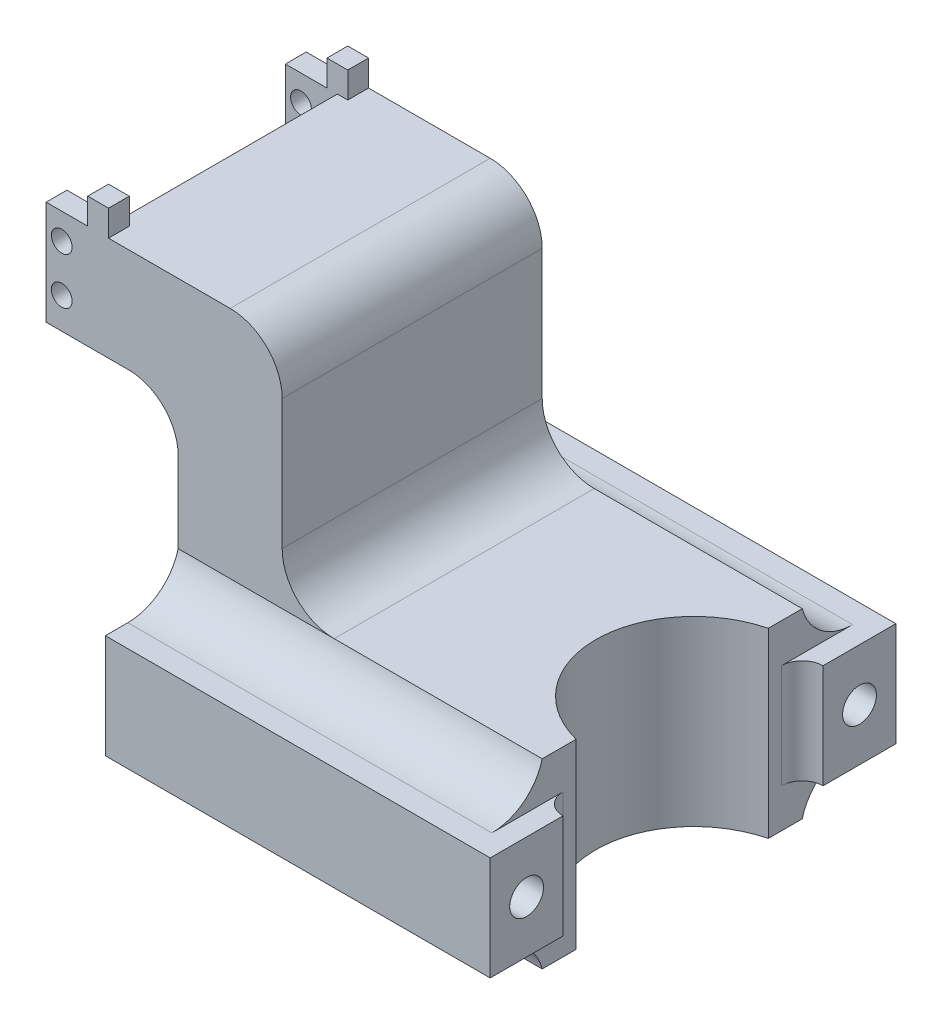
SolidWorks part; units mm, degrees
ref_plane "Front Plane" through (0, 0, 0) normal (0, 0, 1) x (1, 0, 0)
ref_plane "Top Plane" through (0, 0, 0) normal (0, 1, 0) x (1, 0, 0)
ref_plane "Right Plane" through (0, 0, 0) normal (1, 0, 0) x (0, 0, -1)
sketch "Sketch1" plane through (0, 0, 0) normal (0, 1, 0) x (1, 0, 0)
  line L1 (-25, 25) -> (25, 25)
  line L2 (-25, 25) -> (-25, -25)
  line L3 (-25, -25) -> (25, -25)
  line L4 (25, 25) -> (25, -25)
  line L5 (-25, 25) -> (25, -25) construction
  line L6 (-25, -25) -> (25, 25) construction
  ellipse E0 centre (0, 0) end of major axis (19.7, 0) minor radius 19.1
  dimension "D1" = 39.4
  dimension "D2" = 38.2
  dimension "D3" = 50
  dimension "D4" = 50
extrude "Boss-Extrude1" add sketch "Sketch1" along normal blind 35
sketch "Sketch2" plane through (0, 35, 0) normal (0, 1, 0) x (1, 0, 0)
  line L0 (25, 25) -> (-25, 25) construction
  line L1 (-5, 25) -> (25, 25)
  line L2 (-5, 25) -> (-5, -25)
  line L3 (-5, -25) -> (25, -25)
  line L4 (25, 25) -> (25, -25)
  dimension "D1" = 30
extrude "Cut-Extrude1" cut sketch "Sketch2" against normal blind 35
sketch "Sketch3" plane through (0, 35, 0) normal (0, 1, 0) x (1, 0, 0)
  line L0 (-25, -25) -> (-5, -25) construction
  line L1 (-25, 25) -> (-12, 25)
  line L2 (-25, 25) -> (-25, -25)
  line L3 (-25, -25) -> (-12, -25)
  line L4 (-12, 25) -> (-12, -25)
  dimension "D1" = 13
extrude "Boss-Extrude2" add sketch "Sketch3" along normal blind 20
sketch "Sketch4" plane through (-25, 0, 0) normal (-1, 0, 0) x (0, 0, 1)
  line L4 (18.4746, 0) -> (18.4746, 35)
  line L5 (-18.4746, 0) -> (18.4746, 0)
  line L6 (-18.4746, 35) -> (-18.4746, 0)
  line L7 (-15.1475, 35) -> (-18.4746, 35)
  line L8 (18.4746, 0) -> (18.4746, 35)
  line L9 (-18.4746, 0) -> (18.4746, 0)
  line L10 (-18.4746, 35) -> (-18.4746, 0)
  line L11 (-15.1475, 35) -> (-18.4746, 35)
  line L14 (15.1475, 35) -> (-15.1475, 35)
  line L16 (15.1475, 35) -> (-15.1475, 35)
  line L18 (18.4746, 35) -> (15.1475, 35)
  line L20 (18.4746, 35) -> (15.1475, 35)
  circle A0 centre (18.4746, 50) radius 1.5
  dimension "D3" = 3
  dimension "D1" = 0
extrude "Cut-Extrude2" cut sketch "Sketch4" against normal through all contours A0 region at (-25, 50, 18.4746)
ref_plane "Plane1" through (-12, 55, -25) normal (-1, 0, 0) x (0, 0, 1)
sketch "Sketch5" plane through (-12, 55, -25) normal (-1, 0, 0) x (0, 0, 1)
  line L1 (0, 0) -> (36.9746, 0)
  line L2 (0, 0) -> (0, -20)
  line L3 (0, -20) -> (36.9746, -20)
  line L4 (0, -55) -> (50, -55)
  line L5 (50, -55) -> (50, 0)
  line L6 (50, 0) -> (0, 0)
  line L7 (0, 0) -> (0, -55)
  line L8 (0, -55) -> (50, -55)
  line L9 (50, -55) -> (50, 0)
  line L11 (0, 0) -> (0, -55) construction
  line L12 (43.4746, -55) -> (43.4746, -20)
  line L13 (6.5254, -55) -> (43.4746, -55)
  line L14 (6.5254, -20) -> (6.5254, -55)
  line L15 (9.8525, -20) -> (6.5254, -20)
  line L16 (43.4746, -55) -> (43.4746, -20) construction
  line L17 (6.5254, -55) -> (43.4746, -55)
  line L18 (6.5254, -20) -> (6.5254, -55) construction
  line L19 (9.8525, -20) -> (6.5254, -20) construction
  line L20 (36.9746, 0) -> (36.9746, -20)
  line L24 (50, 0) -> (0, 0)
  line L27 (40.1475, -20) -> (9.8525, -20)
  line L28 (40.1475, -20) -> (9.8525, -20)
  line L29 (43.4746, -20) -> (40.1475, -20)
  line L30 (43.4746, -20) -> (40.1475, -20)
  circle A0 centre (43.4746, -5) radius 1.5 construction
  dimension "D3" = 6.5
  dimension "D1" = 0
  dimension "D2" = 0
extrude "Cut-Extrude3" cut sketch "Sketch5" along normal blind 20 contours L20 L1 L2 L3 region at (-12, 45, -6.5127)
sketch "Sketch6" plane through (-5, 0, 0) normal (1, 0, 0) x (0, 0, -1)
  line L0 (-25, 35) -> (-25, 0) construction
  line L1 (25, 0) -> (25, 35) construction
  line L2 (-39, 27.5) -> (-25, 27.5)
  line L3 (-39, 27.5) -> (-39, 7.5)
  line L4 (-39, 7.5) -> (-25, 7.5)
  line L5 (-25, 27.5) -> (-25, 7.5)
  line L6 (-39, 27.5) -> (-25, 7.5) construction
  line L7 (-39, 7.5) -> (-25, 27.5) construction
  line L8 (39, 7.5) -> (25, 7.5)
  line L9 (39, 7.5) -> (39, 27.5)
  line L10 (39, 27.5) -> (25, 27.5)
  line L11 (25, 7.5) -> (25, 27.5)
  line L12 (39, 7.5) -> (25, 27.5) construction
  line L13 (39, 27.5) -> (25, 7.5) construction
  line L14 (32, 17.5) -> (-26.1195, 17.5) construction
  circle A0 centre (32, 17.5) radius 3.25
  circle A1 centre (-32, 17.5) radius 3.25
  point P4 (-32, 17.5)
  point P9 (32, 17.5)
  point P17 (-25, 17.5)
  point P18 (-25, 17.5)
  point P19 (25, 17.5)
  point P20 (25, 17.5)
  dimension "D4" = 6.5
  dimension "D5" = 6.5
  dimension "D2" = 20
  dimension "D1" = 14
  dimension "D3" = 14
extrude "Boss-Extrude3" add sketch "Sketch6" along normal blind 4 and the other way blind 20
sketch "Sketch7" plane through (-25, 0, 0) normal (-1, 0, 0) x (0, 0, 1)
  circle A0 centre (-32, 17.5) radius 5.3
  circle A1 centre (32, 17.5) radius 5.3
  circle A2 centre (18.4746, 50) radius 3
  dimension "D1" = 10.6
  dimension "D2" = 10.6
  dimension "D3" = 6
extrude "Cut-Extrude4" cut sketch "Sketch7" against normal blind 6
sketch "Sketch8" plane through (0, 35, 0) normal (0, 1, 0) x (1, 0, 0)
  line L4 (-12, -11.9746) -> (-25, -11.9746)
  line L5 (-25, -11.9746) -> (-25, -25)
  line L6 (-25, -25) -> (-12, -25)
  line L7 (-12, -25) -> (-12, -11.9746)
  line L8 (-12, -11.9746) -> (-25, -11.9746)
  line L9 (-25, -11.9746) -> (-25, -25)
  line L10 (-25, -25) -> (-12, -25)
  line L11 (-12, -25) -> (-12, -11.9746)
  dimension "D1" = 0
extrude "Cut-Extrude5" cut sketch "Sketch8" along normal blind 30
fillet "Fillet6" radius 4 2 edges at (-5, 17.5, 25) (-5, 17.5, -25)
fillet "Fillet5" radius 10 4 edges at (-15, 7.5, 25) (-15, 27.5, 25) (-15, 27.5, -25) (-15, 7.5, -25)
sketch "Sketch9" plane through (-25, 0, 0) normal (-1, 0, 0) x (0, 0, 1)
  line L8 (39, 27.5) -> (34.6825, 27.5)
  line L9 (25, 35) -> (-25, 35)
  line L10 (-34.6825, 27.5) -> (-39, 27.5)
  line L11 (-39, 27.5) -> (-39, 7.5)
  line L12 (-39, 7.5) -> (-34.6825, 7.5)
  line L13 (-25, 0) -> (25, 0)
  line L14 (34.6825, 7.5) -> (39, 7.5)
  line L15 (39, 7.5) -> (39, 27.5)
  line L16 (39, 27.5) -> (34.6825, 27.5)
  line L17 (25, 35) -> (-25, 35)
  line L18 (-34.6825, 27.5) -> (-39, 27.5)
  line L19 (-39, 27.5) -> (-39, 7.5)
  line L20 (-39, 7.5) -> (-34.6825, 7.5)
  line L21 (-25, 0) -> (25, 0)
  line L22 (34.6825, 7.5) -> (39, 7.5)
  line L23 (39, 7.5) -> (39, 27.5)
  circle A0 centre (32, 17.5) radius 5.3 construction
  circle A1 centre (-32, 17.5) radius 5.3 construction
  circle A2 centre (32, 17.5) radius 5.3
  circle A3 centre (-32, 17.5) radius 5.3
  arc A4 (25, 35) -> (34.6825, 27.5) centre (34.6825, 37.5) ccw
  arc A5 (-34.6825, 27.5) -> (-25, 35) centre (-34.6825, 37.5) ccw
  arc A6 (-25, 0) -> (-34.6825, 7.5) centre (-34.6825, -2.5) ccw
  arc A7 (34.6825, 7.5) -> (25, 0) centre (34.6825, -2.5) ccw
  arc A8 (25, 35) -> (34.6825, 27.5) centre (34.6825, 37.5) ccw
  arc A9 (-34.6825, 27.5) -> (-25, 35) centre (-34.6825, 37.5) ccw
  arc A10 (-25, 0) -> (-34.6825, 7.5) centre (-34.6825, -2.5) ccw
  arc A11 (34.6825, 7.5) -> (25, 0) centre (34.6825, -2.5) ccw
  dimension "D1" = 0
extrude "Boss-Extrude4" add sketch "Sketch9" along normal blind 50
sketch "Sketch10" plane through (0, 35, 0) normal (0, 1, 0) x (1, 0, 0)
  line L5 (-75, -25) -> (-5, -25) construction
  line L6 (-75, 25) -> (-55, 25)
  line L7 (-75, 25) -> (-75, -25)
  line L8 (-75, -25) -> (-55, -25)
  line L9 (-55, 25) -> (-55, -25)
  dimension "D1" = 20
extrude "Boss-Extrude5" add sketch "Sketch10" along normal blind 45
fillet "Fillet7" radius 10 1 edges at (-55, 35, 0)
sketch "Sketch11" plane through (-75, 0, 0) normal (-1, 0, 0) x (0, 0, 1)
  line L5 (25, 80) -> (25, 35) construction
  line L6 (-25, 80) -> (25, 80)
  line L7 (-25, 80) -> (-25, 60)
  line L8 (-25, 60) -> (25, 60)
  line L9 (25, 80) -> (25, 60)
  dimension "D1" = 20
extrude "Boss-Extrude6" add sketch "Sketch11" along normal blind 85
fillet "Fillet8" radius 9.5 1 edges at (-75, 60, 0)
sketch "Sketch13" plane through (0, 80, 0) normal (0, 1, 0) x (1, 0, 0)
  line L0 (-85, 25) -> (-85, -25) construction
  line L1 (-55, 25) -> (-160, 25) construction
  line L2 (-55, 25) -> (-160, 25) construction
  line L3 (-160, -25) -> (-55, -25) construction
  line L4 (-85, 0) -> (-160, 0) construction
  line L5 (-160, 25) -> (-150.4508, 25)
  line L6 (-160, 25) -> (-160, -25)
  line L7 (-160, -25) -> (-150.4508, -25)
  line L8 (-160, -25) -> (-160, 25) construction
  circle A0 centre (-122.5, 0) radius 37.5
  point P4 (-150.4508, 25)
  point P19 (-160, 0)
  line M2 (-55, 25) -> (-160, 25)
  line M14 (-160, -25) -> (-55, -25)
  line M16 (-160, 25) -> (-160, -25)
  dimension "D2" = 75
  dimension "D1" = 75
extrude "Boss-Extrude7" add sketch "Sketch13" against normal up to surface (20 mm away) contours A0 M2 | A0 | A0 region at (-122.5, 80, -30.0791) up to face at (-122.25, 60, 0)
extrude "Cut-Extrude6" cut sketch "Sketch13<3>" against normal blind 85 contours A0 L6 M14 | A0 M2 M16 region at (-157.2108, 80, -18.9204) region at (-157.2108, 80, 18.9204)
sketch "Sketch13<3>" plane through (0, 80, 0) normal (0, 1, 0) x (1, 0, 0) same geometry as "Sketch13"
fillet "Fillet9" radius 10 2 edges at (-94.5492, 70, -25) (-94.5492, 70, 25)
fillet "Fillet10" radius 10 1 edges at (-55, 80, 0)
sketch "Sketch14" plane through (0, 80, 0) normal (0, 1, 0) x (1, 0, 0)
  line L0 (-122.5, 25) -> (-122.5, -25) construction
  line L1 (-122.5, -25) -> (-97.5, 0) construction
  line L2 (-97.5, 0) -> (-122.5, 25) construction
  line L3 (-122.5, 25) -> (-147.5, 0) construction
  line L4 (-147.5, 0) -> (-97.5, 0) construction
  line L5 (-147.5, 0) -> (-122.5, -25) construction
  line L6 (-140.1777, -17.6777) -> (-104.8223, 17.6777) construction
  line L7 (-140.1777, 17.6777) -> (-104.8223, -17.6777) construction
  circle A0 centre (-122.5, 0) radius 25 construction
  circle A1 centre (-140.1777, 17.6777) radius 3.25
  circle A2 centre (-140.1777, -17.6777) radius 3.25
  circle A3 centre (-104.8223, -17.6777) radius 3.25
  circle A4 centre (-104.8223, 17.6777) radius 3.25
  point P10 (-122.5, 0)
  point P13 (-122.5, 0)
  dimension "D4" = 6.5
  dimension "D5" = 6.5
  dimension "D1" = 50
  dimension "D2" = 6.5
  dimension "D3" = 6.5
extrude "Cut-Extrude7" cut sketch "Sketch14" against normal blind 85
sketch "Sketch15" plane through (0, 80, 0) normal (0, 1, 0) x (1, 0, 0)
  circle A0 centre (-140.1777, 17.6777) radius 5.3
  circle A1 centre (-140.1777, -17.6777) radius 5.3
  circle A2 centre (-104.8223, -17.6777) radius 5.3
  circle A3 centre (-104.8223, 17.6777) radius 5.3
  dimension "D1" = 10.6
  dimension "D2" = 10.6
  dimension "D3" = 10.6
  dimension "D4" = 10.6
extrude "Cut-Extrude8" cut sketch "Sketch15" against normal blind 7
sketch "Sketch16" plane through (-75, 0, 0) normal (-1, 0, 0) x (0, 0, 1)
  line L1 (-25.9378, 17.5) -> (-28.9689, 22.75)
  line L2 (-28.9689, 22.75) -> (-35.0311, 22.75)
  line L3 (-35.0311, 22.75) -> (-38.0622, 17.5)
  line L4 (-38.0622, 17.5) -> (-35.0311, 12.25)
  line L5 (-35.0311, 12.25) -> (-28.9689, 12.25)
  line L6 (-28.9689, 12.25) -> (-25.9378, 17.5)
  line L7 (25.9378, 17.5) -> (28.9689, 12.25)
  line L8 (28.9689, 12.25) -> (35.0311, 12.25)
  line L9 (35.0311, 12.25) -> (38.0622, 17.5)
  line L10 (38.0622, 17.5) -> (35.0311, 22.75)
  line L11 (35.0311, 22.75) -> (28.9689, 22.75)
  line L12 (28.9689, 22.75) -> (25.9378, 17.5)
  circle A0 centre (-32, 17.5) radius 5.25 construction
  circle A1 centre (32, 17.5) radius 5.25 construction
  circle A2 centre (32, 17.5) radius 3.25 construction
  circle A3 centre (-32, 17.5) radius 3.25 construction
  circle A4 centre (32, 17.5) radius 3.25
  circle A5 centre (-32, 17.5) radius 3.25
  dimension "D1" = 10.5
  dimension "D2" = 10.5
extrude "Boss-Extrude9" add sketch "Sketch16" against normal up to surface (56 mm away) up to face at (-19, 17.5, -26.7)
extrude "Cut-Extrude11" cut sketch "Sketch16<3>" against normal blind 10
sketch "Sketch16<3>" plane through (-75, 0, 0) normal (-1, 0, 0) x (0, 0, 1) same geometry as "Sketch16"
ref_plane "Plane2" through (-160, 0, 0) normal (-1, 0, 0) x (0, 0, 1)
sketch "Sketch17" plane through (-160, 0, 0) normal (-1, 0, 0) x (0, 0, 1)
  line L1 (-37.5, 80) -> (37.5, 80)
  line L2 (-37.5, 80) -> (-37.5, 60)
  line L3 (-37.5, 60) -> (37.5, 60)
  line L4 (37.5, 80) -> (37.5, 60)
extrude "Cut-Extrude12" cut sketch "Sketch17" against normal up to vertex up to point (-90.3869, 80, -25)
sketch "Sketch19" plane through (-90.3869, 0, 0) normal (-1, 0, 0) x (0, 0, 1)
  line L1 (-25, 80) -> (25, 80)
  line L2 (-25, 80) -> (-25, 60)
  line L3 (-25, 60) -> (25, 60)
  line L4 (25, 80) -> (25, 60)
extrude "Boss-Extrude10" add sketch "Sketch19" along normal blind 10
sketch "Sketch20" plane through (-100.3869, 0, 0) normal (-1, 0, 0) x (0, 0, 1)
  line L0 (25, 80) -> (-25, 80) construction
  line L1 (-21, 80) -> (21, 80)
  line L2 (-21, 80) -> (-21, 60)
  line L3 (-21, 60) -> (21, 60)
  line L4 (21, 80) -> (21, 60)
  line L5 (-25, 60) -> (25, 60) construction
  line L6 (-25, 80) -> (-25, 60) construction
  dimension "D1" = 42
  dimension "D2" = 4
extrude "Cut-Extrude14" cut sketch "Sketch20" against normal blind 10
sketch "Sketch21" plane through (0, 0, -25) normal (0, 0, -1) x (-1, 0, 0)
  line L1 (65, 80) -> (100.3869, 80) construction
  line L2 (100.3869, 80) -> (100.3869, 60) construction
  circle A0 centre (97.3869, 75) radius 2
  circle A1 centre (97.3869, 66) radius 2
  dimension "D1" = 4
  dimension "D3" = 5
  dimension "D2" = 3
  dimension "D4" = 9
extrude "Cut-Extrude15" cut sketch "Sketch21" against normal up to surface (50 mm away) up to face at (-72.5896, 57.4964, 25)
sketch "Sketch22" plane through (0, 80, 0) normal (0, 1, 0) x (1, 0, 0)
  line L0 (-65, 25) -> (-100.3869, 25) construction
  line L1 (-92.3869, 25) -> (-88.3869, 25)
  line L2 (-92.3869, 25) -> (-92.3869, 21)
  line L3 (-92.3869, 21) -> (-88.3869, 21)
  line L4 (-88.3869, 25) -> (-88.3869, 21)
  line L5 (-90.3869, 21) -> (-100.3869, 21) construction
  line L6 (-90.3869, -21) -> (-100.3869, -21) construction
  line L7 (-92.3869, -21) -> (-88.3869, -21)
  line L8 (-92.3869, -21) -> (-92.3869, -25)
  line L9 (-92.3869, -25) -> (-88.3869, -25)
  line L10 (-88.3869, -21) -> (-88.3869, -25)
  line L11 (-100.3869, -25) -> (-65, -25) construction
  line L12 (-100.3869, -25) -> (-100.3869, -21) construction
  line L13 (-100.3869, 21) -> (-100.3869, 25) construction
  dimension "D1" = 8
  dimension "D2" = 8
  dimension "D3" = 4
  dimension "D4" = 4
extrude "Boss-Extrude11" add sketch "Sketch22" along normal blind 5
sketch "Sketch25" plane through (0, 0, 0) normal (0, -1, 0) x (1, 0, 0)
  line L1 (-75, -25) -> (-75, 25) construction
  line L3 (-75, 25) -> (-5, 25) construction
  circle A0 centre (-40, 17.5) radius 2.5
  circle A1 centre (-40, -17.5) radius 2.5
  point P4 (0, 0)
  point P6 (0, 0)
  dimension "D2" = 5
  dimension "D1" = 35
  dimension "D3" = 7.5
  dimension "D4" = 35
extrude "Cut-Extrude16" cut sketch "Sketch25" against normal blind 3.81
equation "\"D3@Sketch6\"=\"D1@Sketch6\""
equation "\"D5@Sketch6\"=\"D4@Sketch6\""
equation "\"D2@Sketch7\"=\"D1@Sketch7\""
equation "\"D3@Sketch14\"=\"D2@Sketch14\""
equation "\"D4@Sketch14\"=\"D2@Sketch14\""
equation "\"D5@Sketch14\"=\"D2@Sketch14\""
equation "\"D3@Sketch15\"=\"D1@Sketch15\""
equation "\"D4@Sketch15\"=\"D1@Sketch15\""
equation "\"D2@Sketch15\"=\"D1@Sketch15\""
equation "\"D2@Sketch16\"=\"D1@Sketch16\""
